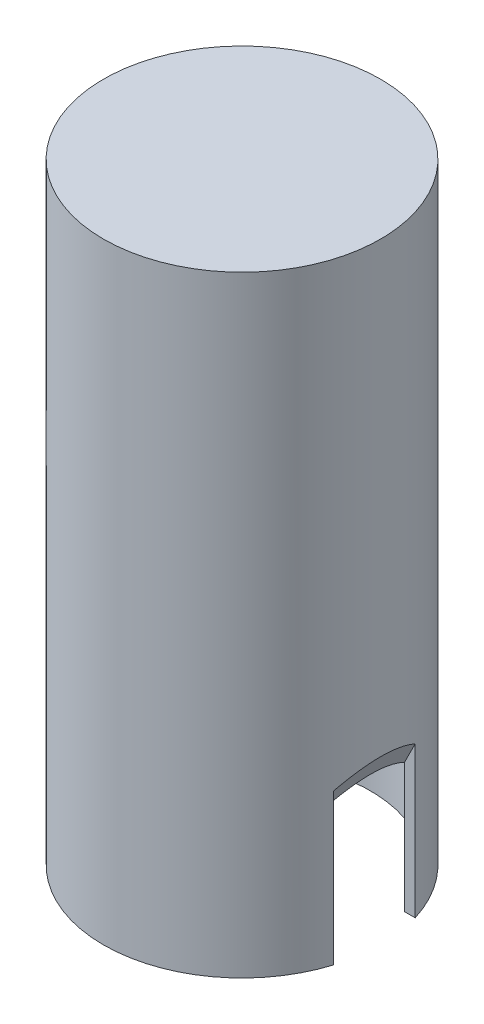
SolidWorks part; units mm, degrees
ref_plane "Front Plane" through (0, 0, 0) normal (0, 0, 1) x (1, 0, 0)
ref_plane "Top Plane" through (0, 0, 0) normal (0, 1, 0) x (1, 0, 0)
ref_plane "Right Plane" through (0, 0, 0) normal (1, 0, 0) x (0, 0, -1)
sketch "Sketch3" plane through (0, 0, 0) normal (0, 1, 0) x (1, 0, 0)
  circle A0 centre (0, 0) radius 68
  dimension "D1" = 136
extrude "Boss-Extrude1" add sketch "Sketch3" along normal blind 300
ref_axis "Axis1" through (0, 300, 0) along (0, -1, 0)
shell "Shell1" thickness 5 removed face at (0, 0, 68)
sketch "Sketch8" plane through (0, 0, 0) normal (0, 0, 1) x (1, 0, 0)
  line L0 (-68, 0) -> (-58, 0)
  line L1 (-68, 0) -> (68, 0) construction
  line L2 (-58, 0) -> (-58, 60)
  line L4 (-68, 300) -> (-68, 0) construction
  line L5 (-68, 80) -> (-68, 0)
  line L6 (-58, 60) -> (-68, 80)
  line L7 (0, -74.8) -> (0, 74.8) construction
  line L8 (68, 0) -> (58, 0)
  line L9 (58, 0) -> (58, 60)
  line L10 (58, 60) -> (68, 80)
  line L11 (68, 80) -> (68, 0)
  dimension "D1" = 10
  dimension "D2" = 80
  dimension "D3" = 60
extrude "Cut-Extrude3" cut sketch "Sketch8" against normal blind 20 and the other way blind 20
